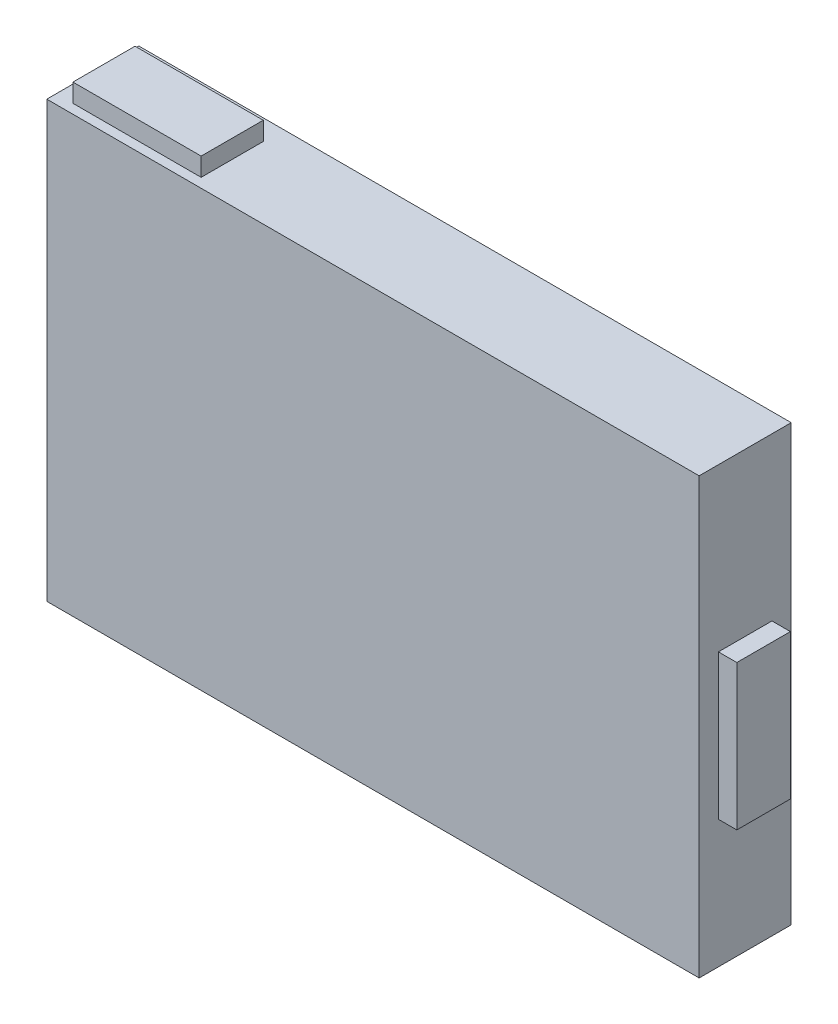
SolidWorks part; units mm, degrees
ref_plane "Front Plane" through (0, 0, 0) normal (0, 0, 1) x (1, 0, 0)
ref_plane "Top Plane" through (0, 0, 0) normal (0, 1, 0) x (1, 0, 0)
ref_plane "Right Plane" through (0, 0, 0) normal (1, 0, 0) x (0, 0, -1)
sketch "Sketch1" plane through (0, 0, 0) normal (0, 0, 1) x (1, 0, 0)
  line L1 (-89.2089, 64.73) -> (90.7911, 64.73)
  line L2 (-89.2089, 64.73) -> (-89.2089, -55.27)
  line L3 (-89.2089, -55.27) -> (90.7911, -55.27)
  line L4 (90.7911, 64.73) -> (90.7911, -55.27)
extrude "Boss-Extrude2" add sketch "Sketch1" along normal blind 25.4
sketch "Sketch2" plane through (0, -55.27, 0) normal (0, -1, 0) x (1, 0, 0)
  line L1 (82.5, 5.3766) -> (-82.5, 5.3766)
  line L2 (82.5, 5.3766) -> (82.5, 20.8525)
  line L3 (82.5, 20.8525) -> (-82.5, 20.8525)
  line L4 (-82.5, 5.3766) -> (-82.5, 20.8525)
  line L5 (82.5, 5.3766) -> (-82.5, 20.8525) construction
  line L6 (82.5, 20.8525) -> (-82.5, 5.3766) construction
  point P0 (0, 13.1145)
extrude "Cut-Extrude2" cut sketch "Sketch2" against normal blind 25.4
sketch "Sketch3" plane through (0, 64.73, 0) normal (0, 1, 0) x (1, 0, 0)
  line L1 (-49.2293, -22.787) -> (-84.6028, -22.787)
  line L2 (-49.2293, -22.787) -> (-49.2293, -5.6529)
  line L3 (-49.2293, -5.6529) -> (-84.6028, -5.6529)
  line L4 (-84.6028, -22.787) -> (-84.6028, -5.6529)
  line L5 (-49.2293, -22.787) -> (-84.6028, -5.6529) construction
  line L6 (-49.2293, -5.6529) -> (-84.6028, -22.787) construction
  point P0 (-66.916, -14.22)
extrude "Cut-Extrude3" cut sketch "Sketch3" against normal blind 25.4
sketch "Sketch4" plane through (90.7911, 0, 0) normal (1, 0, 0) x (0, 0, -1)
  line L1 (-5.3088, -20) -> (-20.0912, -20)
  line L2 (-5.3088, -20) -> (-5.3088, 20)
  line L3 (-5.3088, 20) -> (-20.0912, 20)
  line L4 (-20.0912, -20) -> (-20.0912, 20)
  line L5 (-5.3088, -20) -> (-20.0912, 20) construction
  line L6 (-5.3088, 20) -> (-20.0912, -20) construction
  point P0 (-12.7, 0)
extrude "Cut-Extrude4" cut sketch "Sketch4" against normal blind 25.4
extrude "Boss-Extrude3" add sketch "Sketch3<2>" along normal blind 5.08 separate body
sketch "Sketch3<2>" plane through (0, 64.73, 0) normal (0, 1, 0) x (1, 0, 0) same geometry as "Sketch3"
extrude "Boss-Extrude4" add sketch "Sketch4<2>" along normal blind 5.08 separate body
sketch "Sketch4<2>" plane through (90.7911, 0, 0) normal (1, 0, 0) x (0, 0, -1) same geometry as "Sketch4"
